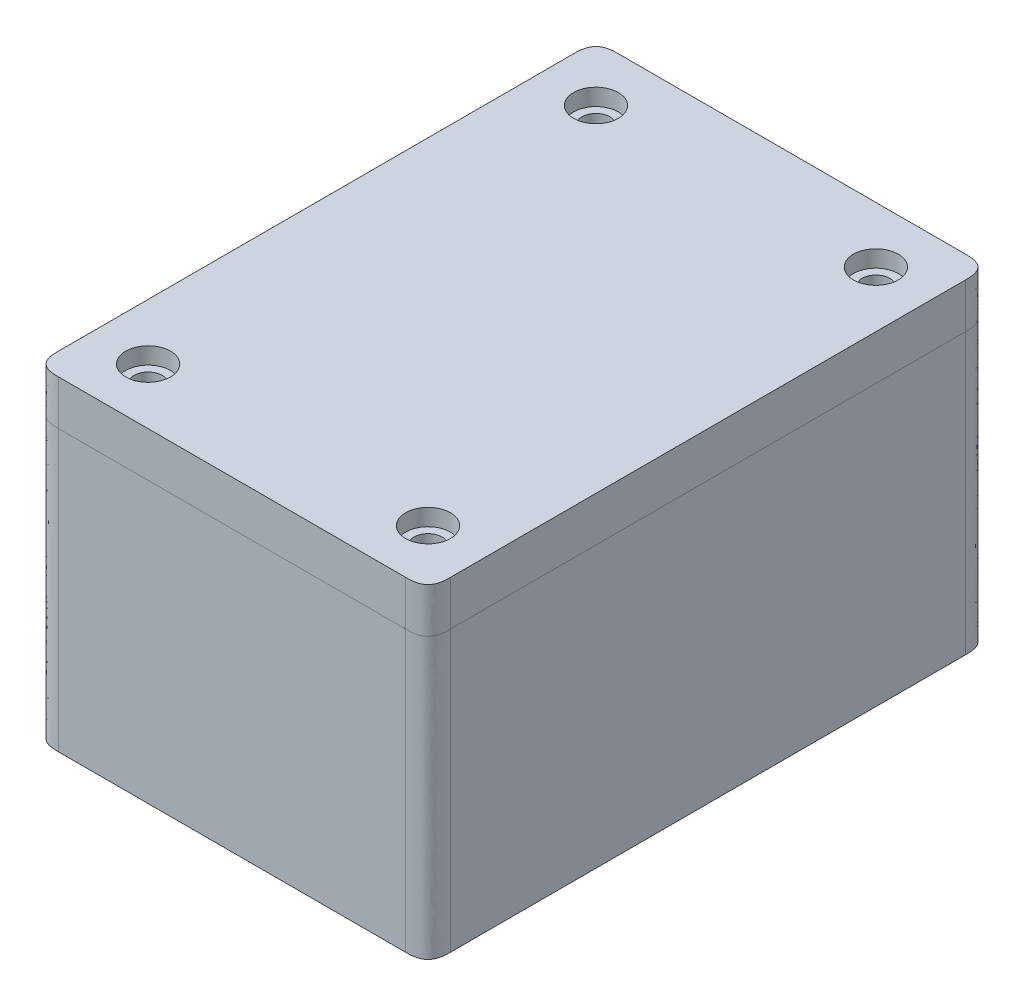
SolidWorks part; units mm, degrees
ref_plane "Front Plane" through (0, 0, 0) normal (0, 0, 1) x (1, 0, 0)
ref_plane "Top Plane" through (0, 0, 0) normal (0, 1, 0) x (1, 0, 0)
ref_plane "Right Plane" through (0, 0, 0) normal (1, 0, 0) x (0, 0, -1)
sketch "Sketch1" plane through (0, 0, 0) normal (0, 1, 0) x (1, 0, 0)
  line L1 (0, 0) -> (70, 0)
  line L2 (0, 0) -> (0, 100)
  line L3 (0, 100) -> (70, 100)
  line L4 (70, 0) -> (70, 100)
  dimension "Length_box" = 100
  dimension "width_box" = 70
extrude "Boss-Extrude1" add sketch "Sketch1" against normal blind 50
shell "Shell1" thickness 5 removed face at (35, 0, -50)
sketch "Sketch2" plane through (0, 0, 0) normal (0, 1, 0) x (1, 0, 0)
  line L0 (15, 10) -> (5, 10) construction
  line L1 (5, 5) -> (15, 5)
  line L2 (5, 5) -> (5, 15)
  line L3 (5, 15) -> (15, 15)
  line L4 (15, 5) -> (15, 15)
  line L5 (10, 15) -> (10, 5) construction
  circle A0 centre (10, 10) radius 2
  point P11 (9, 9.3317)
  point P12 (9, 9)
  point P13 (0, 0)
  point P14 (0, 0)
  dimension "D3" = 4
  dimension "D1" = 10
  dimension "D2" = 10
extrude "Boss-Extrude2" add sketch "Sketch2" against normal up to next contours L1 L4 L3 L2 A0 | A0 region at (5.1414, 0, -10) region at (10, 0, -10)
extrude "Cut-Extrude1" cut sketch "Sketch2<3>" against normal blind 6 contours A0 region at (10, 0, -10)
sketch "Sketch2<3>" plane through (0, 0, 0) normal (0, 1, 0) x (1, 0, 0) same geometry as "Sketch2"
ref_plane "Plane1" through (35, 0, 0) normal (-1, 0, 0) x (0, 0, 1)
ref_plane "Plane2" through (0, 0, -50) normal (0, 0, -1) x (-1, 0, 0)
mirror "Mirror1" about plane through (0, 0, -50) normal (0, 0, -1) of "Cut-Extrude1", "Boss-Extrude2"
mirror "Mirror2" about plane through (35, 0, 0) normal (-1, 0, 0) of "Mirror1"
fillet "Fillet2" radius 4 4 edges at (55, -22.5, -15) (55, -22.5, -85) (15, -22.5, -85) (15, -22.5, -15) curvature continuous yes
fillet "Fillet3" radius 2 8 edges at (5, -22.5, -85) (15, -22.5, -95) (55, -22.5, -95) (65, -22.5, -85) (5, -22.5, -15) (15, -22.5, -5) (65, -22.5, -15) (55, -22.5, -5) curvature continuous yes
fillet "Fillet4" radius 4 4 edges at (0, -25, 0) (0, -25, -100) (70, -25, -100) (70, -25, 0) curvature continuous yes
sketch "Sketch8" plane through (0, -45, 0) normal (0, 1, 0) x (1, 0, 0)
  circle A0 centre (20, 30) radius 4
  circle A1 centre (20, 30) radius 2
  dimension "D3" = 8
  dimension "D4" = 4
  dimension "D1" = 20
  dimension "D2" = 30
extrude "Boss-Extrude6" add sketch "Sketch8" along normal blind 12
pattern_linear "LPattern1" count 2 spacing 40 along (0, 0, -1) count 2 spacing 30 along (1, 0, 0) of "Boss-Extrude6"
sketch "Sketch5" plane through (0, 0, -100) normal (0, 0, -1) x (-1, 0, 0)
  line L1 (-66, 0) -> (-4, 0) construction
  circle A0 centre (-35, -25) radius 5
  point P2 (0, 0)
  point P4 (-35, -19.7189)
  point P5 (-35, -24.7178)
  point P6 (-35, -22.1344)
  dimension "D3" = 10
  dimension "D1" = 35
  dimension "D2" = 25
extrude "Cut-Extrude4" cut sketch "Sketch5" against normal up to next contours A0
extrude "Boss-Extrude4" add sketch "Sketch1<2>" along normal blind 8 separate body
sketch "Sketch1<2>" plane through (0, 0, 0) normal (0, 1, 0) x (1, 0, 0) same geometry as "Sketch1"
sketch "Sketch6" plane through (0, 8, 0) normal (0, 1, 0) x (1, 0, 0)
  line L0 (70, 0) -> (70, 100) construction
  line L1 (70, 100) -> (0, 100) construction
  circle A0 centre (10, 10) radius 2.5
  circle A1 centre (60, 10) radius 2.5
  circle A2 centre (60, 90) radius 2.5
  circle A3 centre (10, 90) radius 4
  circle A4 centre (10, 90) radius 2.5
  circle A5 centre (60, 90) radius 4
  circle A6 centre (60, 10) radius 4
  circle A7 centre (10, 10) radius 4
  dimension "D1" = 10
  dimension "D2" = 10
  dimension "D5" = 8
  dimension "D6" = 5
  dimension "D3" = 10
  dimension "D4" = 10
extrude "Cut-Extrude2" cut sketch "Sketch6" against normal blind 3
extrude "Cut-Extrude3" cut sketch "Sketch6<3>" against normal up to next (8 mm away) contours A4 | A2 | A0 | A1 region at (10, 8, -10) region at (60, 8, -90) region at (10, 8, -90)
sketch "Sketch6<3>" plane through (0, 8, 0) normal (0, 1, 0) x (1, 0, 0) same geometry as "Sketch6"
fillet "Fillet5" radius 4 4 edges at (70, 4, -100) (70, 4, 0) (0, 4, 0) (0, 4, -100) curvature continuous yes
equation "\"box_thickness\" = 5"
equation "\"D4@Shell1\"=\"box_thickness\""
equation "\"D2@Shell1\"=\"box_thickness\""
equation "\"D3@Shell1\"=\"box_thickness\""
equation "\"D5@Shell1\"=\"box_thickness\""
equation "\"post_width\"=10"
equation "\"D1@Sketch2\"=\"post_width\""
equation "\"D2@Sketch2\"=\"post_width\""
equation "\"D1@Sketch6\"=\"box_thickness\"+\"post_width\"/2"
equation "\"D2@Sketch6\"=\"D1@Sketch6\""
equation "\"D3@Sketch6\"=\"D1@Sketch6\""
equation "\"D4@Sketch6\"=\"D1@Sketch6\""
equation "\"stud_height\" = 12"
equation "\"D1@Boss-Extrude6\"=\"stud_height\""
